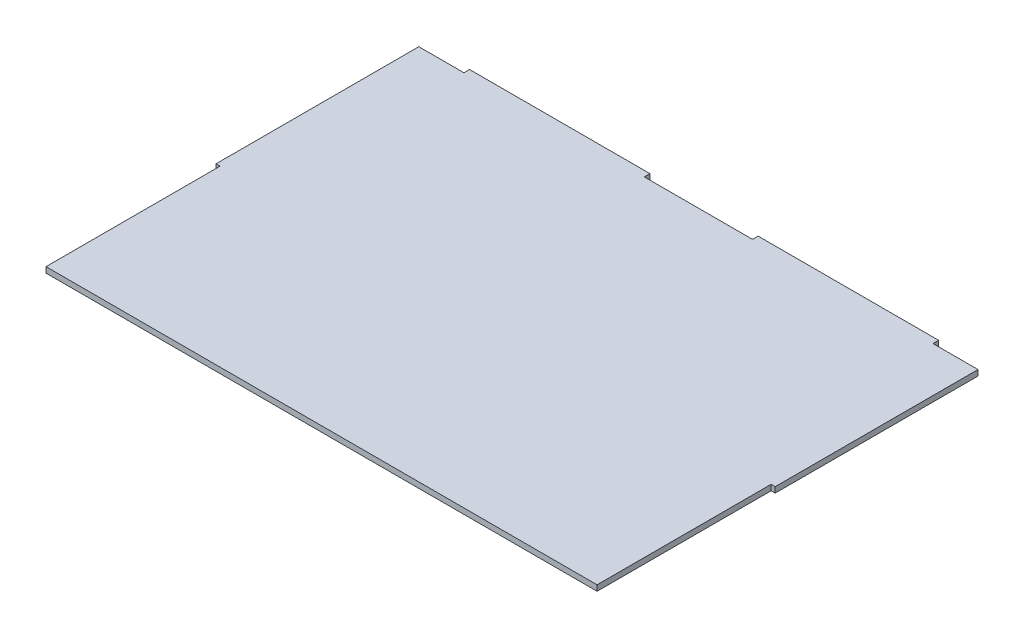
SolidWorks part; units mm, degrees
material "Custom Plastic"
ref_plane "X-Y Datum" through (0, 0, 0) normal (0, 0, 1) x (1, 0, 0)
ref_plane "X-Z Datum" through (0, 0, 0) normal (0, 1, 0) x (1, 0, 0)
ref_plane "Y-Z Datum" through (0, 0, 0) normal (1, 0, 0) x (0, 0, -1)
sketch "Sketch1" plane through (0, 0, 0) normal (0, 0, 1) x (1, 0, 0)
  line L1 (-157.4823, -1.5875) -> (157.4823, -1.5875)
  line L2 (-157.4823, -1.5875) -> (-157.4823, 1.5875)
  line L3 (-157.4823, 1.5875) -> (157.4823, 1.5875)
  line L4 (157.4823, -1.5875) -> (157.4823, 1.5875)
  line L5 (-157.4823, -1.5875) -> (157.4823, 1.5875) construction
  line L6 (-157.4823, 1.5875) -> (157.4823, -1.5875) construction
  point P0 (0, 0)
  dimension "D1" = 314.9646
  dimension "D2" = 3.175
extrude "Boss-Extrude1" add sketch "Sketch1" along normal blind 235.775
sketch "Sketch3" plane through (0, 0, 0) normal (0, 0, -1) x (-1, 0, 0)
  line L0 (-157.4823, 0) -> (-81.2823, 0) construction
  line L1 (-157.4823, -1.5875) -> (-157.4823, 1.5875) construction
  line L2 (-157.4823, 1.5875) -> (157.4823, 1.5875) construction
  line L3 (-132.0823, -1.5875) -> (-30.4823, -1.5875)
  line L4 (-132.0823, -1.5875) -> (-132.0823, 1.5875)
  line L5 (-132.0823, 1.5875) -> (-30.4823, 1.5875)
  line L6 (-30.4823, -1.5875) -> (-30.4823, 1.5875)
  line L7 (-132.0823, -1.5875) -> (-30.4823, 1.5875) construction
  line L8 (-132.0823, 1.5875) -> (-30.4823, -1.5875) construction
  line L14 (-157.4823, 1.5875) -> (-132.0823, 1.5875)
  line L15 (-157.4823, 1.5875) -> (-157.4823, -1.5875)
  line L16 (-157.4823, -1.5875) -> (-132.0823, -1.5875)
  line L17 (-132.0823, 1.5875) -> (-132.0823, -1.5875)
  line L19 (-30.4823, 1.5875) -> (-30.4823, -1.5875)
  line L20 (0, 43.0151) -> (0, -43.0151) construction
  line L21 (30.4823, -1.5875) -> (30.4823, 1.5875)
  line L22 (132.0823, -1.5875) -> (132.0823, 1.5875)
  line L23 (132.0823, 1.5875) -> (30.4823, 1.5875)
  line L24 (132.0823, -1.5875) -> (30.4823, 1.5875) construction
  line L25 (132.0823, -1.5875) -> (30.4823, -1.5875)
  line L26 (132.0823, 1.5875) -> (30.4823, -1.5875) construction
  line M2 (-157.4823, 1.5875) -> (-157.4823, -1.5875)
  line M3 (-157.4823, -1.5875) -> (157.4823, -1.5875)
  line M4 (157.4823, -1.5875) -> (157.4823, 1.5875)
  line M5 (157.4823, 1.5875) -> (-157.4823, 1.5875)
  dimension "D1" = 76.2
  dimension "D2" = 101.6
extrude "Cut-Extrude1" cut sketch "Sketch3" against normal blind 3.175 contours L4 M3 M5 M2 | L6 M3 M5 | M3 M4 M5 region at (144.7823, 0, 0) region at (0, 0, 0) region at (-144.7823, 0, 0)
sketch "Sketch5" plane through (0, 1.5875, 0) normal (0, 1, 0) x (1, 0, 0)
  line L1 (-157.4823, -235.775) -> (-155.1963, -235.775)
  line L3 (-157.4823, -235.775) -> (-157.4823, -117.411)
  line L5 (-157.4823, -117.411) -> (-155.1963, -117.411)
  line L6 (-155.1963, -235.775) -> (-155.1963, -117.411)
  line M11 (-157.4823, -3.175) -> (-157.4823, -235.775)
  line M12 (-157.4823, -235.775) -> (157.4823, -235.775)
  dimension "D1" = 118.364
  dimension "D2" = 2.286
extrude "Cut-Extrude2" cut sketch "Sketch5" against normal blind 3.175 and the other way through all contours M12 M11 region at (-156.3393, 1.5875, 176.593)
mirror "Mirror1" about plane through (0, 0, 0) normal (1, 0, 0) of "Cut-Extrude2"
sketch "Sketch6" plane through (0, 1.5875, 0) normal (0, 1, 0) x (1, 0, 0)
  line L6 (-157.4823, -215.455) -> (-81.2823, -215.455)
  line L7 (-157.4823, -215.455) -> (-157.4823, -235.775)
  line L8 (-157.4823, -235.775) -> (-81.2823, -235.775)
  line L9 (-81.2823, -215.455) -> (-81.2823, -235.775)
  line L10 (155.1963, -235.775) -> (-155.1963, -235.775) construction
  line L11 (-157.4823, -117.411) -> (-157.4823, -3.175) construction
  line L13 (155.1963, -235.775) -> (-81.2823, -235.775)
  line L14 (155.1963, -235.775) -> (155.1963, -215.455)
  line L15 (155.1963, -215.455) -> (-81.2823, -215.455)
  line L16 (-81.2823, -235.775) -> (-81.2823, -215.455)
  line M18 (-155.1963, -117.411) -> (-155.1963, -235.775)
  line M19 (-155.1963, -235.775) -> (155.1963, -235.775)
  line M20 (155.1963, -235.775) -> (155.1963, -117.411)
  dimension "D1" = 76.2
  dimension "D2" = 20.32
extrude "Cut-Extrude4" cut sketch "Sketch6" against normal through all contours L9 L6 M18 M19 | L15 L9 M20 M19 region at (-118.2393, 1.5875, 225.615) region at (36.957, 1.5875, 225.615)
mirror "Mirror2" [suppressed] about plane through (0, 0, 0) normal (1, 0, 0)
